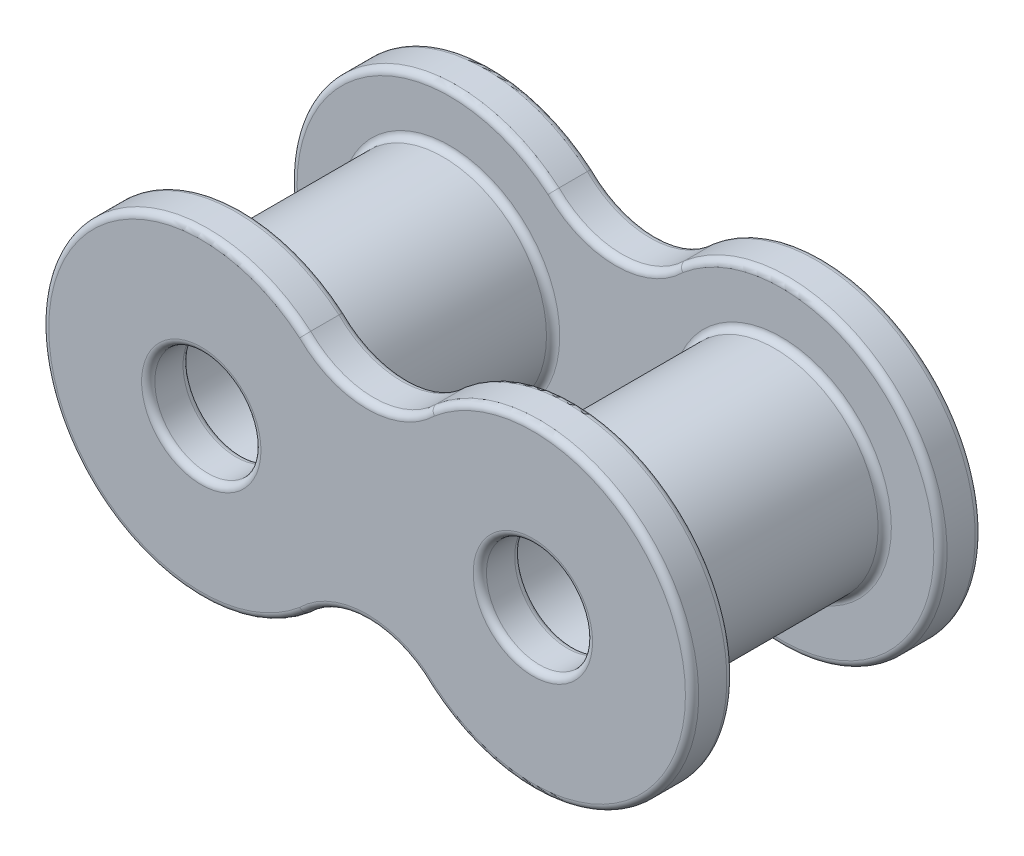
SolidWorks part; units mm, degrees
ref_plane "Front Plane" through (0, 0, 0) normal (0, 0, 1) x (1, 0, 0)
ref_plane "Top Plane" through (0, 0, 0) normal (0, 1, 0) x (1, 0, 0)
ref_plane "Right Plane" through (0, 0, 0) normal (1, 0, 0) x (0, 0, -1)
sketch "Sketch1" plane through (0, 0, 0) normal (0, 0, 1) x (1, 0, 0)
  line L0 (-25.6447, 0) -> (57.1423, 0)
  line L1 (0, 33.9639) -> (0, -30.9921)
  circle A0 centre (-6.35, 0) radius 2.032
  arc A1 (-2.4117, 4.6531) -> (-2.4117, -4.6531) centre (-6.35, 0) ccw
  circle A2 centre (6.35, 0) radius 2.032
  arc A3 (2.4117, 4.6531) -> (2.4117, -4.6531) centre (6.35, 0) cw
  arc A6 (2.4117, 4.6531) -> (-2.4117, 4.6531) centre (0, 7.0648) cw
  arc A7 (2.4117, -4.6531) -> (-2.4117, -4.6531) centre (0, -7.0648) ccw
  dimension "D1" = 4.064
  dimension "D2" = 12.192
  dimension "D3" = 6.35
extrude "Boss-Extrude2" add sketch "Sketch1" along normal blind 1.5875 contours L1 A6 A1 L0 A0 | A7 L1 L0 A0 A1 | A7 A3 L0 A2 L1 | A3 A6 L1 L0 A2 region at (-6.0721, 2.7897, 0) region at (-6.0721, -2.7897, 0) region at (6.0721, 2.7897, 0) region at (6.0721, -2.7897, 0)
fillet "Fillet10" radius 0.254 12 edges at (-4.318, 0, 1.5875) (-12.446, 0, 1.5875) (0, 3.6541, 1.5875) (12.446, 0, 1.5875) (0, -3.6541, 1.5875) (8.382, 0, 1.5875) (-4.318, 0, 0) (12.446, 0, 0) (0, 3.6541, 0) (-12.446, 0, 0) (0, -3.6541, 0) (8.382, 0, 0)
sketch "Sketch2" plane through (0, 0, 0) normal (0, 0, -1) x (-1, 0, 0)
  circle A0 centre (-6.35, 0) radius 3.9624
  circle A1 centre (-6.35, 0) radius 2.032 construction
  circle A2 centre (-6.35, 0) radius 2.032 construction
  circle A3 centre (-6.35, 0) radius 2.032
  circle A4 centre (-6.35, 0) radius 2.032
  circle M7 centre (-6.35, 0) radius 2.286
  dimension "D1" = 7.9248
extrude "Boss-Extrude3" add sketch "Sketch2" along normal blind 7.9248 contours A0 M7 region at (10.2003, 0, 0)
mirror "Mirror1" about plane through (0, 0, 0) normal (1, 0, 0) of "Boss-Extrude3"
ref_plane "Plane2" through (0, 0, -3.9624) normal (0, 0, -1) x (-1, 0, 0)
mirror "Mirror4" about plane through (0, 0, -3.9624) normal (0, 0, -1) of "Boss-Extrude2"
fillet "Fillet11" radius 0.254 12 edges at (2.3876, 0, -7.9248) (-2.3876, 0, -7.9248) (-12.446, 0, -7.9248) (0, 3.6541, -7.9248) (12.446, 0, -7.9248) (0, -3.6541, -7.9248) (-4.318, 0, -9.5123) (12.446, 0, -9.5123) (0, 3.6541, -9.5123) (-12.446, 0, -9.5123) (0, -3.6541, -9.5123) (8.382, 0, -9.5123)
